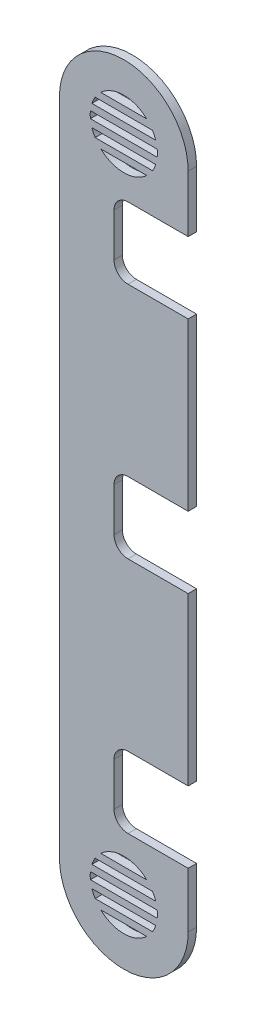
SolidWorks part; units mm, degrees
ref_plane "Front Plane" through (0, 0, 0) normal (0, 0, 1) x (1, 0, 0)
ref_plane "Top Plane" through (0, 0, 0) normal (0, 1, 0) x (1, 0, 0)
ref_plane "Right Plane" through (0, 0, 0) normal (1, 0, 0) x (0, 0, -1)
sketch "Sketch1" plane through (0, 0, 0) normal (0, 0, 1) x (1, 0, 0)
  line L0 (-23.5, 139.9624) -> (-23.5, 114.5)
  line L1 (-43, 160.25) -> (-43, -75.25)
  line L2 (3, 160.25) -> (3, 139.9624)
  line L4 (-23.5, -30.0376) -> (3, -30.0376)
  line L6 (-23.5, -55.5) -> (3, -55.5)
  line L8 (-23.5, 54.9624) -> (3, 54.9624)
  line L10 (-23.5, 29.5) -> (3, 29.5)
  line L12 (-23.5, 139.9624) -> (3, 139.9624)
  line L14 (-23.5, 114.5) -> (3, 114.5)
  line L16 (-23.5, 54.9624) -> (-23.5, 29.5)
  line L17 (-23.5, -30.0376) -> (-23.5, -55.5)
  line L24 (3, -55.5) -> (3, -75.25)
  line L25 (3, 29.5) -> (3, -30.0376)
  line L26 (3, 114.5) -> (3, 54.9624)
  arc A2 (3, 160.25) -> (-43, 160.25) centre (-20, 160.25) ccw
  arc A3 (-43, -75.25) -> (3, -75.25) centre (-20, -75.25) ccw
extrude "Boss-Extrude1" add sketch "Sketch1" along normal blind 3
fillet "Fillet1" radius 5 6 edges at (-23.5, 139.9624, 1.5) (-23.5, 114.5, 1.5) (-23.5, 54.9624, 1.5) (-23.5, 29.5, 1.5) (-23.5, -55.5, 1.5) (-23.5, -30.0376, 1.5)
sketch "Sketch2" plane through (0, 0, 3) normal (0, 0, 1) x (1, 0, 0)
  line L0 (-20, 183.25) -> (-20, -98.25) construction
  line L1 (-20, 42.5) -> (-43, 42.5) construction
  line L2 (-43, 160.25) -> (-43, -75.25) construction
  line L3 (3, 84.7312) -> (-20, 84.7312) construction
  line L4 (3, 54.9624) -> (3, 114.5) construction
  line L5 (-32, 160.25) -> (-8, 160.25) construction
  line L6 (-31.9347, 161.5) -> (-8.0653, 161.5)
  line L7 (-31.399, 164) -> (-8.601, 164)
  line L8 (-30.2439, 166.5) -> (-9.7561, 166.5)
  line L9 (-28.212, 169) -> (-11.788, 169)
  line L10 (-31.9347, 159) -> (-8.0653, 159)
  line L11 (-28.212, 151.5) -> (-11.788, 151.5)
  line L12 (-30.2439, 154) -> (-9.7561, 154)
  line L13 (-31.399, 156.5) -> (-8.601, 156.5)
  line L14 (-32, -75.25) -> (-8, -75.25) construction
  line L15 (-31.399, -71.5) -> (-8.601, -71.5)
  line L16 (-30.2439, -69) -> (-9.7561, -69)
  line L17 (-28.212, -66.5) -> (-11.788, -66.5)
  line L18 (-31.9347, -74) -> (-8.0653, -74)
  line L19 (-28.212, -84) -> (-11.788, -84)
  line L20 (-30.2439, -81.5) -> (-9.7561, -81.5)
  line L21 (-31.399, -79) -> (-8.601, -79)
  line L22 (-31.9347, -76.5) -> (-8.0653, -76.5)
  arc A0 (3, 160.25) -> (-43, 160.25) centre (-20, 160.25) ccw construction
  arc A1 (-43, -75.25) -> (3, -75.25) centre (-20, -75.25) ccw construction
  arc A2 (-30.2439, 166.5) -> (-31.399, 164) centre (-20, 160.25) ccw
  arc A3 (-11.788, 169) -> (-28.212, 169) centre (-20, 160.25) ccw
  arc A4 (-8.601, 164) -> (-9.7561, 166.5) centre (-20, 160.25) ccw
  arc A5 (-31.9347, 161.5) -> (-31.9347, 159) centre (-20, 160.25) ccw
  arc A6 (-31.399, 156.5) -> (-30.2439, 154) centre (-20, 160.25) ccw
  arc A7 (-8.0653, 159) -> (-8.0653, 161.5) centre (-20, 160.25) ccw
  arc A8 (-9.7561, 154) -> (-8.601, 156.5) centre (-20, 160.25) ccw
  arc A9 (-28.212, 151.5) -> (-11.788, 151.5) centre (-20, 160.25) ccw
  arc A10 (-28.212, -66.5) -> (-11.788, -66.5) centre (-20, -75.25) cw
  arc A11 (-9.7561, -69) -> (-8.601, -71.5) centre (-20, -75.25) cw
  arc A12 (-8.0653, -74) -> (-8.0653, -76.5) centre (-20, -75.25) cw
  arc A13 (-31.399, -71.5) -> (-30.2439, -69) centre (-20, -75.25) cw
  arc A14 (-31.9347, -76.5) -> (-31.9347, -74) centre (-20, -75.25) cw
  arc A15 (-8.601, -79) -> (-9.7561, -81.5) centre (-20, -75.25) cw
  arc A16 (-11.788, -84) -> (-28.212, -84) centre (-20, -75.25) cw
  arc A17 (-30.2439, -81.5) -> (-31.399, -79) centre (-20, -75.25) cw
  dimension "D1" = 1.25
  dimension "D2" = 2.5
  dimension "D3" = 2.5
  dimension "D4" = 2.5
extrude "Cut-Extrude1" cut sketch "Sketch2" against normal up to surface (3 mm away) up to face at (-14.5551, 42.2801, 0)
